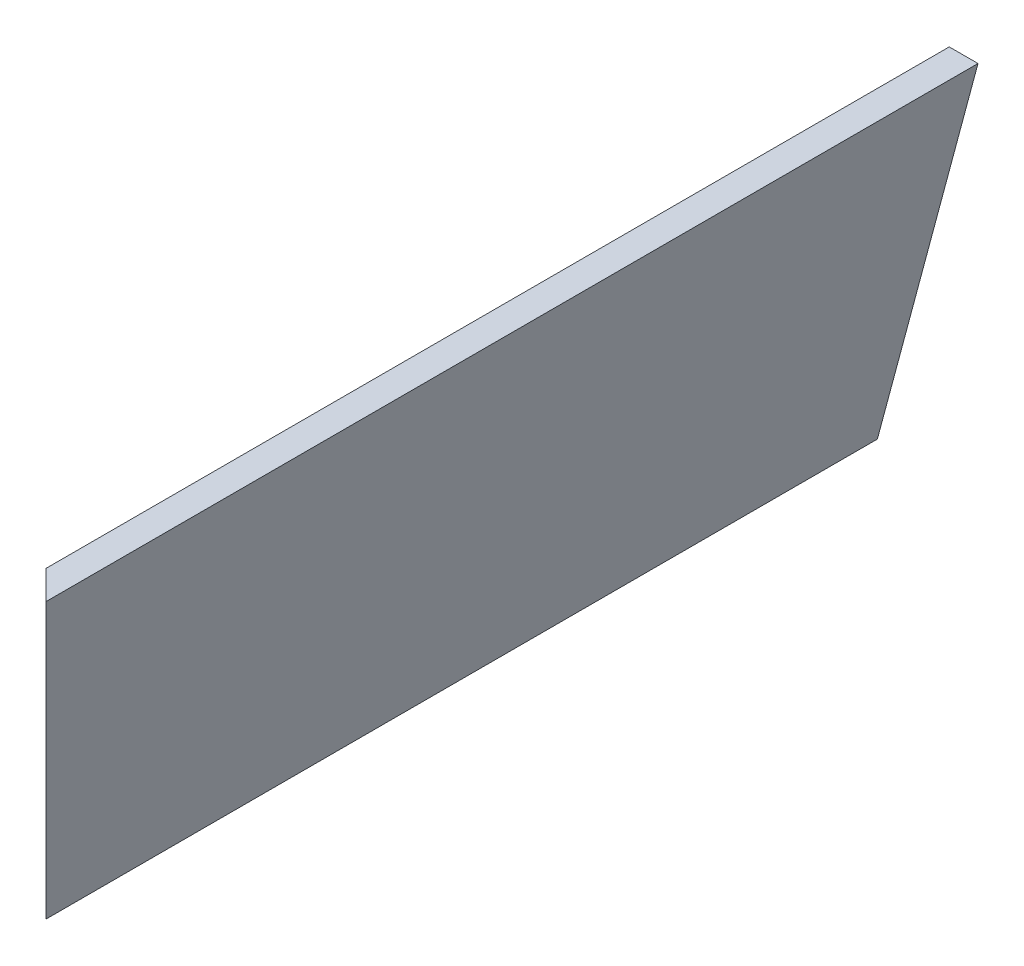
SolidWorks part; units mm, degrees
material "Cedar"
ref_plane "Front Plane" through (0, 0, 0) normal (0, 0, 1) x (1, 0, 0)
ref_plane "Top Plane" through (0, 0, 0) normal (0, 1, 0) x (1, 0, 0)
ref_plane "Right Plane" through (0, 0, 0) normal (1, 0, 0) x (0, 0, -1)
ref_plane "Plane1" through (0, 0, 0) normal (-0.7071, 0, 0.7071) x (0.7071, 0, 0.7071)
sketch "Sketch2" plane through (0, 0, 0) normal (0, 0, 1) x (1, 0, 0)
  line L0 (366.9376, 0) -> (380.0856, 0)
  line L1 (380.0856, 0) -> (426.1036, 171.7416)
  line L2 (426.1036, 171.7416) -> (412.9556, 171.7416)
  line L3 (412.9556, 171.7416) -> (366.9376, 0)
  line L4 (0, 0) -> (366.9376, 0) construction
  line L5 (366.9376, 0) -> (366.9376, 177.6975) construction
  dimension "D1" = 15
  dimension "D2" = 12.7
  dimension "D3" = 177.8
  dimension "D4" = 380.0856
extrude "Boss-Extrude1" add sketch "Sketch2" along normal up to surface (426.1036 mm away) up to plane "Plane1"
mirror "Mirror1" [suppressed] about plane through (0, 0, 0) normal (-0.7071, 0, 0.7071)
